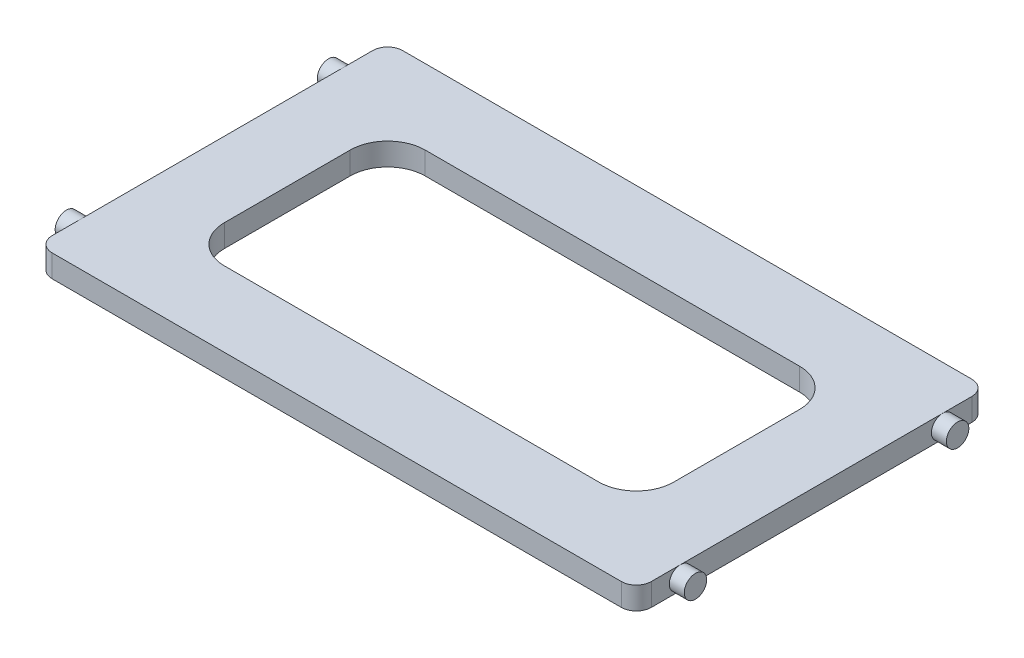
SolidWorks part; units mm, degrees
material "Copper"
ref_plane "Front Plane" through (0, 0, 0) normal (0, 0, 1) x (1, 0, 0)
ref_plane "Top Plane" through (0, 0, 0) normal (0, 1, 0) x (1, 0, 0)
ref_plane "Right Plane" through (0, 0, 0) normal (1, 0, 0) x (0, 0, -1)
sketch "Sketch1" plane through (0, 0, 0) normal (0, 1, 0) x (1, 0, 0)
  line L1 (0, 0) -> (101.6, 0)
  line L2 (0, 0) -> (0, 59.436)
  line L3 (0, 59.436) -> (101.6, 59.436)
  line L4 (101.6, 0) -> (101.6, 59.436)
  dimension "D1" = 59.436
  dimension "D2" = 101.6
extrude "Base Extrude" add sketch "Sketch1" along normal blind 3.81
fillet "Base Corner Fillet" radius 2.54 4 edges at (0, 1.905, 0) (0, 1.905, -59.436) (101.6, 1.905, -59.436) (101.6, 1.905, 0)
sketch "Sketch3" plane through (0, 0, 0) normal (-1, 0, 0) x (0, 0, 1)
  line L0 (-29.718, 3.81) -> (-29.718, 0) construction
  line L1 (-56.896, 3.81) -> (-2.54, 3.81) construction
  line L2 (-56.896, 0) -> (-2.54, 0) construction
  line L3 (0, 1.905) -> (-59.436, 1.905) construction
  line L4 (0, 3.81) -> (0, 0) construction
  line L5 (-59.436, 0) -> (-59.436, 3.81) construction
  circle A0 centre (-7.493, 1.905) radius 1.905
  circle A1 centre (-51.943, 1.905) radius 1.905
  dimension "D1" = 3.81
  dimension "D2" = 22.225
extrude "Peg Extrude" add sketch "Sketch3" along normal blind 2.54
ref_plane "Peg Mirror Plane" through (50.8, 0, 0) normal (1, 0, 0) x (0, 0, -1)
mirror "Peg Mirror" about plane through (50.8, 0, 0) normal (1, 0, 0) of "Peg Extrude"
sketch "Sketch4" plane through (0, 0, 0) normal (0, -1, 0) x (1, 0, 0)
  line L0 (2.54, 0) -> (99.06, 0) construction
  line L1 (19.05, -12.7) -> (82.55, -12.7)
  line L2 (12.7, -19.05) -> (12.7, -40.386)
  line L3 (19.05, -46.736) -> (82.55, -46.736)
  line L4 (88.9, -19.05) -> (88.9, -40.386)
  line L5 (99.06, -59.436) -> (2.54, -59.436) construction
  line L6 (0, -51.943) -> (0, -7.493) construction
  line L7 (101.6, -7.493) -> (101.6, -51.943) construction
  arc A0 (82.55, -12.7) -> (88.9, -19.05) centre (82.55, -19.05) cw
  arc A1 (82.55, -46.736) -> (88.9, -40.386) centre (82.55, -40.386) ccw
  arc A2 (12.7, -40.386) -> (19.05, -46.736) centre (19.05, -40.386) ccw
  arc A3 (19.05, -12.7) -> (12.7, -19.05) centre (19.05, -19.05) ccw
  dimension "D5" = 6.35
  dimension "D1" = 12.7
  dimension "D2" = 12.7
  dimension "D3" = 12.7
  dimension "D4" = 12.7
extrude "Material Removal Cut" cut sketch "Sketch4" against normal through all
